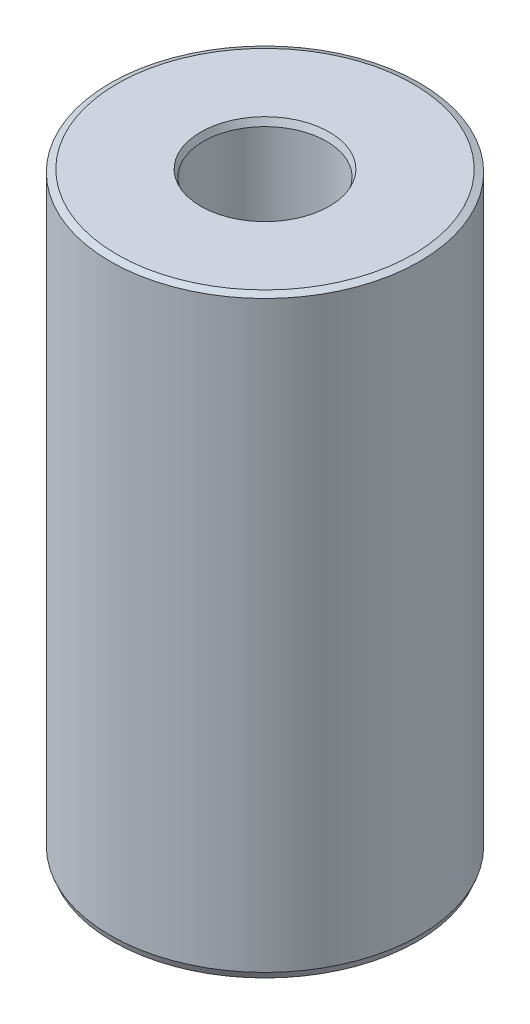
SolidWorks part; units mm, degrees
ref_plane "Front Plane" through (0, 0, 0) normal (0, 0, 1) x (1, 0, 0)
ref_plane "Top Plane" through (0, 0, 0) normal (0, 1, 0) x (1, 0, 0)
ref_plane "Right Plane" through (0, 0, 0) normal (1, 0, 0) x (0, 0, -1)
sketch "Sketch1" plane through (0, 0, 0) normal (0, 1, 0) x (1, 0, 0)
  circle A0 centre (0, 0) radius 25
  dimension "SLEEVE_OD" = 50
extrude "Boss-Extrude1" add sketch "Sketch1" along normal blind 95.874
sketch "Sketch2" plane through (0, 0, 0) normal (0, 1, 0) x (1, 0, 0)
  circle A0 centre (0, 0) radius 9.9629
  dimension "BORE_D" = 19.9258
extrude "Cut-Extrude1" cut sketch "Sketch2" along normal through all
chamfer "Chamfer1" distance 0.4338 angle 68.2 4 edges at (0, 95.874, 9.9629) (0, 0, 9.9629) (0, 0, 25) (0, 95.874, 25) first distance on face at (0, 95.874, 9.9629) first distance on face at (0, 0, 9.9629) first distance on face at (0, 95.874, 25)
